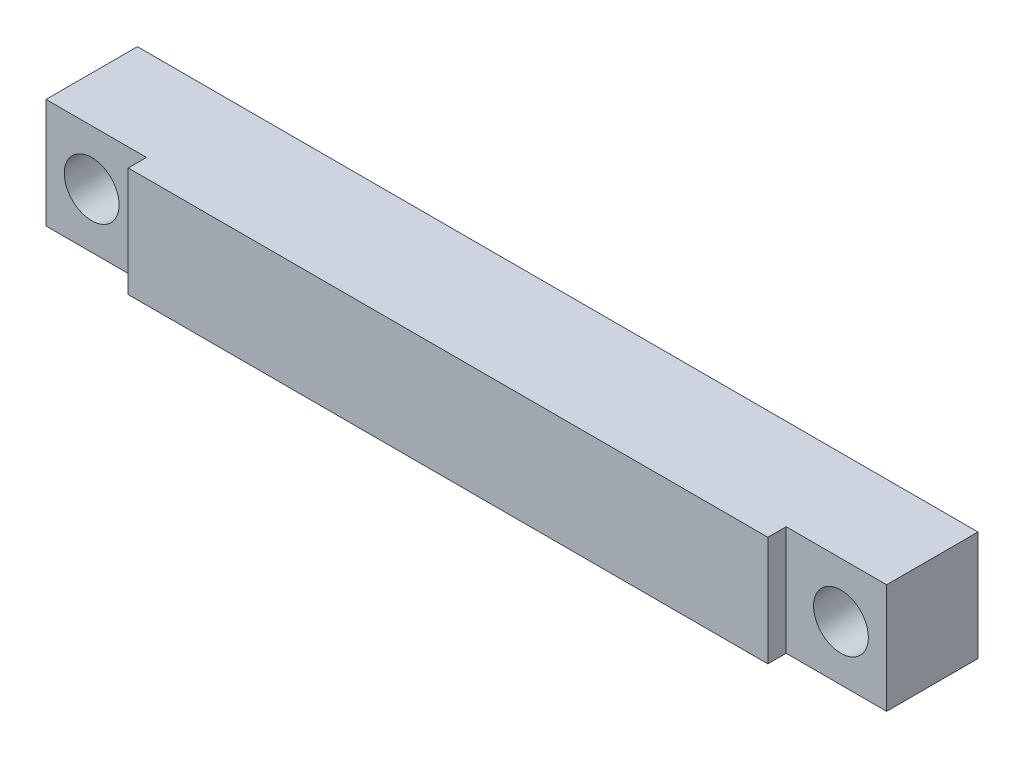
SolidWorks part; units mm, degrees
ref_plane "Front Plane" through (0, 0, 0) normal (0, 0, 1) x (1, 0, 0)
ref_plane "Top Plane" through (0, 0, 0) normal (0, 1, 0) x (1, 0, 0)
ref_plane "Right Plane" through (0, 0, 0) normal (1, 0, 0) x (0, 0, -1)
sketch "Sketch1" plane through (0, 0, 0) normal (0, 0, 1) x (1, 0, 0)
  line L0 (0, -55) -> (0, 55) construction
  line L1 (-23, 3) -> (23, 3)
  line L2 (-23, 3) -> (-23, -3)
  line L3 (-23, -3) -> (23, -3)
  line L4 (23, 3) -> (23, -3)
  line L5 (-23, 3) -> (23, -3) construction
  line L6 (-23, -3) -> (23, 3) construction
  line L7 (-17.5, 3) -> (-17.5, -3)
  line L8 (17.5, 3) -> (17.5, -3)
  circle A0 centre (-20.5, 0) radius 1.5
  circle A1 centre (20.5, 0) radius 1.5
  point P0 (0, 0)
  dimension "D3" = 20.5
  dimension "D1" = 46
  dimension "D2" = 6
  dimension "D4" = 3
  dimension "D5" = 35
  dimension "D6" = 17.5
extrude "Boss-Extrude1" add sketch "Sketch1" along normal blind 5 contours L7 L1 L2 L3 A0 | L1 L8 L3 L4 A1 | L8 L1 L7 L3 region at (-20.25, 2.9186, 0) region at (0, 0, 0) region at (20.25, 2.9186, 0)
extrude "Boss-Extrude2" add sketch "Sketch1<3>" along normal blind 6 contours L8 L1 L7 L3 region at (0, 0, 0)
sketch "Sketch1<3>" plane through (0, 0, 0) normal (0, 0, 1) x (1, 0, 0) same geometry as "Sketch1"
